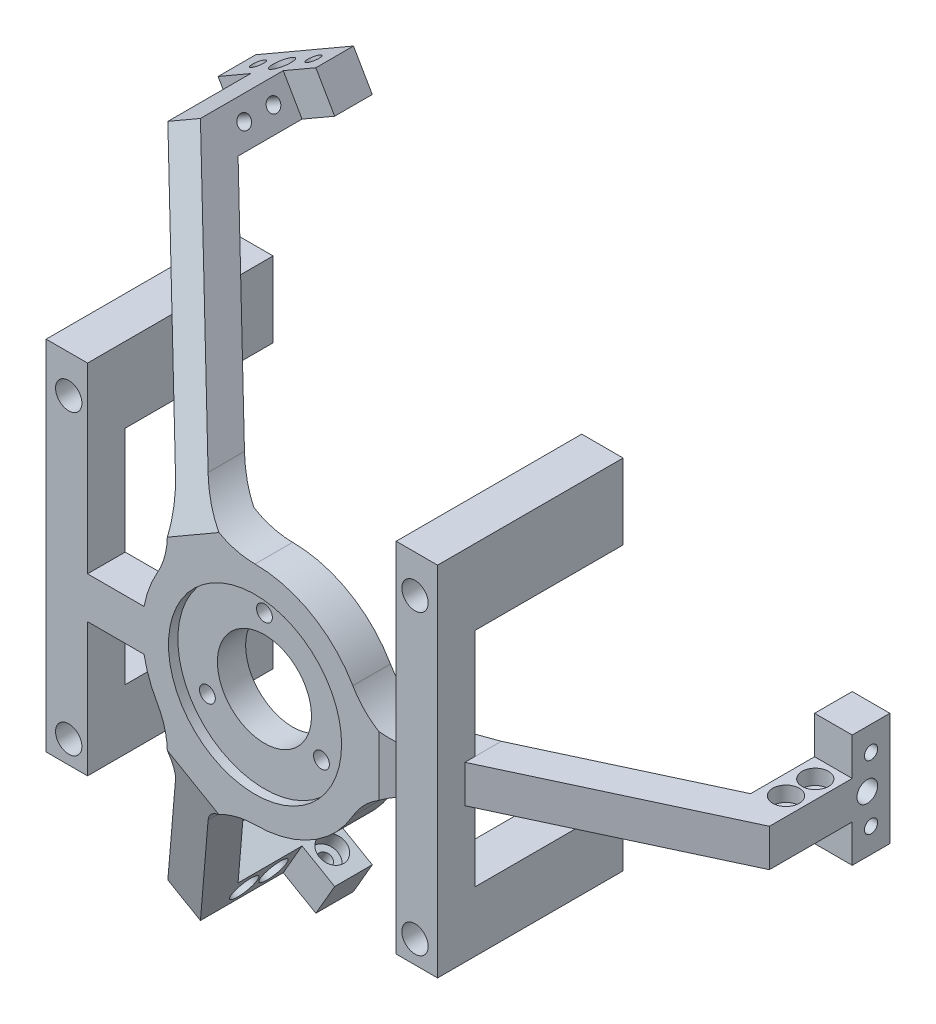
SolidWorks part; units mm, degrees
ref_plane "Plan de face" through (0, 0, 0) normal (0, 0, 1) x (1, 0, 0)
ref_plane "Plan de dessus" through (0, 0, 0) normal (0, 1, 0) x (1, 0, 0)
ref_plane "Plan de droite" through (0, 0, 0) normal (1, 0, 0) x (0, 0, -1)
sketch "Esquisse1" plane through (0, 0, 0) normal (0, 0, 1) x (1, 0, 0)
  line L0 (0, 0) -> (93.67, 0) construction
  line L1 (93.67, 15) -> (103.67, 15)
  line L2 (93.67, 15) -> (93.67, -15)
  line L3 (93.67, -15) -> (103.67, -15)
  line L4 (103.67, 15) -> (103.67, -15)
  line L5 (-33.8446, -88.6206) -> (-59.8254, -73.6206)
  line L6 (-33.8446, -88.6206) -> (-38.8446, -97.2809)
  line L7 (-38.8446, -97.2809) -> (-64.8254, -82.2809)
  line L8 (-59.8254, -73.6206) -> (-64.8254, -82.2809)
  line L9 (-59.8254, 73.6206) -> (-33.8446, 88.6206)
  line L10 (-59.8254, 73.6206) -> (-64.8254, 82.2809)
  line L11 (-64.8254, 82.2809) -> (-38.8446, 97.2809)
  line L12 (-33.8446, 88.6206) -> (-38.8446, 97.2809)
  point P17 (0, 0)
  dimension "D1" = 30
  dimension "D2" = 10
  dimension "D3" = 93.67
  dimension "D4" = 3
extrude "Boss.-Extru.1" add sketch "Esquisse1" along normal blind 10
sketch "Esquisse2" plane through (0, 0, 10) normal (0, 0, 1) x (1, 0, 0)
  line L0 (-57.0272, 86.7831) -> (-46.3532, 92.9458)
  line L1 (-38.8446, 97.2809) -> (-64.8254, 82.2809) construction
  line L2 (93.67, 15) -> (93.67, -15) construction
  line L3 (93.67, 5) -> (103.67, 5)
  line L4 (93.67, 5) -> (93.67, -5)
  line L5 (93.67, -5) -> (103.67, -5)
  line L6 (103.67, 5) -> (103.67, -5)
  line L7 (103.67, -15) -> (103.67, 15) construction
  line L8 (-42.5049, -83.6206) -> (-51.1651, -78.6206)
  line L9 (-42.5049, -83.6206) -> (-47.5049, -92.2809)
  line L10 (-47.5049, -92.2809) -> (-56.1651, -87.2809)
  line L11 (-51.1651, -78.6206) -> (-56.1651, -87.2809)
  line L12 (-51.1651, 78.6206) -> (-42.5049, 83.6206)
  line L13 (-51.1651, 78.6206) -> (-56.1651, 87.2809)
  line L14 (-56.1651, 87.2809) -> (-47.5049, 92.2809)
  line L15 (-42.5049, 83.6206) -> (-47.5049, 92.2809)
  point P12 (93.67, 0)
  point P13 (93.67, 0)
  point P24 (0, 0)
  line M6 (-59.8254, 73.6206) -> (-33.8446, 88.6206)
  dimension "D1" = 3
extrude "Boss.-Extru.2" add sketch "Esquisse2" along normal blind 45 contours L15 L0 L13 M6 | L6 L3 L4 L5 | L8 L11 L10 L9 region at (-49.335, 85.4507, 10) region at (98.67, 0, 10) region at (-49.335, -85.4507, 10)
sketch "Esquisse3" plane through (0, 0, 55) normal (0, 0, 1) x (1, 0, 0)
  line L0 (103.67, 5) -> (103.67, -5) construction
  line L1 (-47.5049, -92.2809) -> (-56.1651, -87.2809) construction
  line L2 (-47.5049, 92.2809) -> (-56.1651, 87.2809) construction
  line L3 (103.67, 5) -> (103.67, -5)
  line L4 (-47.5049, -92.2809) -> (-56.1651, -87.2809)
  line L5 (-47.5049, 92.2809) -> (-56.1651, 87.2809)
  line L6 (-56.1651, -87.2809) -> (-19.1203, -23.1174)
  line L7 (-47.5049, -92.2809) -> (-10.4601, -28.1174)
  line L8 (103.67, -5) -> (29.5804, -5)
  line L9 (103.67, 5) -> (29.5804, 5)
  line L10 (-56.1651, 87.2809) -> (-19.1203, 23.1174)
  line L11 (-47.5049, 92.2809) -> (-10.4601, 28.1174)
  line L12 (-51.1651, -78.6206) -> (-56.1651, -87.2809) construction
  line L13 (-42.5049, -83.6206) -> (-47.5049, -92.2809) construction
  line L14 (93.67, -5) -> (103.67, -5) construction
  line L15 (93.67, 5) -> (103.67, 5) construction
  line L16 (-51.1651, 78.6206) -> (-56.1651, 87.2809) construction
  line L17 (-42.5049, 83.6206) -> (-47.5049, 92.2809) construction
  arc A0 (-19.1203, -23.1174) -> (-19.1203, 23.1174) centre (0, 0) cw
  arc A1 (-10.4601, 28.1174) -> (29.5804, 5) centre (0, 0) cw
  arc A2 (29.5804, -5) -> (-10.4601, -28.1174) centre (0, 0) cw
  dimension "D1" = 30
extrude "Boss.-Extru.3" add sketch "Esquisse3" along normal blind 10
chamfer "Chanfrein1" distance 28 angle 65 3 edges at (93.67, 0, 55) (-46.835, -81.1206, 55) (-46.835, 81.1206, 55) first distance on face at (93.67, 0, 18.75) first distance on face at (-46.835, -81.1206, 18.75) first distance on face at (-46.835, 81.1206, 18.75)
chamfer "Chanfrein2" distance 33 angle 65 3 edges at (-51.835, -89.7809, 65) (-51.835, 89.7809, 65) (103.67, 0, 65) first distance on face at (-51.835, -89.7809, 21.25) first distance on face at (-51.835, 89.7809, 21.25) first distance on face at (103.67, 0, 21.25)
fillet "Congé1" radius 20 6 edges at (29.5804, -5, 60) (-10.4601, -28.1174, 60) (-19.1203, -23.1174, 60) (-19.1203, 23.1174, 60) (29.5804, 5, 60) (-10.4601, 28.1174, 60)
sketch "Esquisse4" plane through (0, 0, 65) normal (0, 0, 1) x (1, 0, 0)
  circle A0 centre (0, 0) radius 12.5
  dimension "D1" = 25
extrude "Enlèv. mat.-Extru.1" cut sketch "Esquisse4" against normal up to next
sketch "Esquisse5" plane through (0, 0, 65) normal (0, 0, 1) x (1, 0, 0)
  circle A0 centre (0, 0) radius 23
  dimension "D1" = 46
extrude "Enlèv. mat.-Extru.2" cut sketch "Esquisse5" against normal blind 2.5
sketch "Esquisse6" plane through (0, 0, 62.5) normal (0, 0, 1) x (1, 0, 0)
  line L0 (0, 17.5) -> (0, 0) construction
  circle A0 centre (0, 17.5) radius 2.1
  circle A1 centre (15.1554, -8.75) radius 2.1
  circle A2 centre (-15.1554, -8.75) radius 2.1
  point P10 (0, 0)
  dimension "D2" = 4.2
  dimension "D1" = 17.5
  dimension "D3" = 3
extrude "Enlèv. mat.-Extru.3" cut sketch "Esquisse6" against normal up to next
sketch "Esquisse7" plane through (0, 0, 55) normal (0, 0, -1) x (-1, 0, 0)
  line L0 (0, 0) -> (44.5, 0) construction
  line L1 (-37.5, -41) -> (-48.5, -41)
  line L2 (-37.5, -41) -> (-37.5, 54)
  line L3 (-37.5, 54) -> (-48.5, 54)
  line L4 (-48.5, -41) -> (-48.5, 54)
  line L5 (55.5, -41) -> (44.5, -41)
  line L6 (44.5, -41) -> (44.5, -5.5)
  line L7 (44.5, -5.5) -> (29.4915, -5.5)
  line L8 (55.5, -41) -> (55.5, 54)
  line L9 (55.5, 54) -> (44.5, 54)
  line L10 (44.5, 54) -> (44.5, 5.5)
  line L11 (44.5, 5.5) -> (29.4915, 5.5)
  line L12 (44.5, -5.5) -> (44.5, 5.5) construction
  arc A0 (25.9808, -15) -> (25.9808, 15) centre (0, 0) ccw construction
  arc A1 (29.4915, -5.5) -> (29.4915, 5.5) centre (0, 0) ccw
  point P7 (-43, 54)
  point P22 (44.5, 0)
  point P28 (50, 54)
  dimension "D1" = 11
  dimension "D2" = 41
  dimension "D3" = 95
  dimension "D4" = 43
  dimension "D5" = 93
extrude "Boss.-Extru.4" add sketch "Esquisse7" along normal blind 39.3 and the other way up to surface (10 mm away) other way up to face at (23, 0, 65)
sketch "Esquisse8" plane through (0, 0, 15.7) normal (0, 0, -1) x (-1, 0, 0)
  line L0 (-48.5, 6.5) -> (55.5, 6.5) construction
  line L1 (-48.5, 54) -> (-48.5, -41) construction
  line L2 (55.5, -41) -> (55.5, 54) construction
  line L3 (49.5, 44) -> (-42.5, 44) construction
  line L4 (3.5, 6.5) -> (3.5, 44) construction
  line L5 (-48.5, -41) -> (-37.5, -41) construction
  circle A0 centre (49.5, 44) radius 1.75
  circle A1 centre (-42.5, 44) radius 1.75
  circle A2 centre (-42.5, -35) radius 1.75
  circle A3 centre (49.5, -35) radius 1.75
  dimension "D4" = 3.5
  dimension "D1" = 92
  dimension "D2" = 79
  dimension "D3" = 6
extrude "Enlèv. mat.-Extru.4" cut sketch "Esquisse8" against normal up to next
sketch "Esquisse9" plane through (0, 0, 65) normal (0, 0, 1) x (1, 0, 0)
  circle A0 centre (42.5, -35) radius 3.5
  circle A1 centre (42.5, 44) radius 3.5
  circle A2 centre (-49.5, -35) radius 3.5
  circle A3 centre (-49.5, 44) radius 3.5
  dimension "D1" = 7
extrude "Enlèv. mat.-Extru.5" cut sketch "Esquisse9" against normal offset from surface (28.3 mm away) 21 up to face at (40.75, -35, 15.7)
sketch "Esquisse10" plane through (0, 0, 15.7) normal (0, 0, -1) x (-1, 0, 0)
  line L6 (55.5, -41) -> (55.5, 54) construction
  line L7 (55.5, -25) -> (29.4915, -25)
  line L8 (55.5, -25) -> (55.5, 34)
  line L9 (55.5, 34) -> (29.4915, 34)
  line L10 (29.4915, -25) -> (29.4915, 34)
  line L11 (49.5, 44) -> (49.5, 34) construction
  line L12 (49.5, -35) -> (49.5, -25) construction
  line L13 (-48.5, 54) -> (-48.5, -41) construction
  line L14 (-48.5, 34) -> (-37.5, 34)
  line L15 (-48.5, 34) -> (-48.5, -25)
  line L16 (-48.5, -25) -> (-37.5, -25)
  line L17 (-37.5, 34) -> (-37.5, -25)
  line L18 (-37.5, -41) -> (-37.5, 54) construction
  dimension "D1" = 10
extrude "Enlèv. mat.-Extru.6" cut sketch "Esquisse10" against normal up to surface (39.3 mm away) up to face at (-2.1, 17.5, 55)
sketch "Esquisse17" plane through (0, 0, 55) normal (0, 0, -1) x (-1, 0, 0)
  line L0 (-37.5, -5.8599) -> (-48.5, -5)
  line L1 (-48.5, -5) -> (-48.5, 5)
  line L2 (-48.5, 5) -> (-37.5, 5.8599)
  line L3 (-37.5, 5.8599) -> (-37.5, -5.8599)
extrude "Boss.-Extru.5" add sketch "Esquisse17" along normal up to surface (6.9369 mm away) contours L3 L0 L1 L2 up to face at (71.085, 0, 37.5316)
sketch "Esquisse11" plane through (4.3301, -2.5, 0) normal (0.866, -0.5, 0) x (0, 0, -1)
  line L0 (-27, -93.67) -> (-10, -93.67) construction
  line L1 (-10, -93.67) -> (-10, -103.67) construction
  circle A0 centre (-15, -98.86) radius 1.75
  circle A1 centre (-22.78, -98.86) radius 1.75
  dimension "D4" = 3.5
  dimension "D1" = 5.19
  dimension "D2" = 5
  dimension "D3" = 7.78
extrude "Enlèv. mat.-Extru.7" cut sketch "Esquisse11" against normal up to next
sketch "Esquisse12" plane through (4.3301, -2.5, 0) normal (0.866, -0.5, 0) x (0, 0, -1)
  circle A0 centre (-15, -98.86) radius 3.5
  circle A1 centre (-22.78, -98.86) radius 3.5
  dimension "D1" = 7
extrude "Enlèv. mat.-Extru.8" cut sketch "Esquisse12" against normal blind 4
sketch "Esquisse13" plane through (-46.835, -81.1206, 0) normal (0.5, 0.866, 0) x (0.866, -0.5, 0)
  line L0 (-15, -10) -> (-15, 0) construction
  line L1 (-15, -5) -> (-8.5, -5) construction
  line L2 (15, -5) -> (8.5, -5) construction
  line L3 (15, -10) -> (15, 0) construction
  circle A0 centre (-8.5, -5) radius 1.75
  circle A1 centre (8.5, -5) radius 1.75
  dimension "D2" = 3.5
  dimension "D1" = 6.5
extrude "Enlèv. mat.-Extru.9" cut sketch "Esquisse13" against normal up to next
sketch "Esquisse14" plane through (-46.835, -81.1206, 0) normal (0.5, 0.866, 0) x (0.866, -0.5, 0)
  circle A0 centre (-8.5, -5) radius 3.5
  circle A1 centre (8.5, -5) radius 3.5
  dimension "D1" = 7
extrude "Enlèv. mat.-Extru.10" cut sketch "Esquisse14" against normal blind 4
sketch "Esquisse15" plane through (-46.835, -81.1206, 0) normal (0.5, 0.866, 0) x (0.866, -0.5, 0)
  line L0 (15, 0) -> (-15, 0) construction
  line L1 (-15, -10) -> (-15, 0) construction
  circle A0 centre (0, -6) radius 2.75
  point P5 (0, 0)
  point P8 (-15, -5)
  dimension "D1" = 5.5
  dimension "D2" = 1
extrude "Enlèv. mat.-Extru.11" cut sketch "Esquisse15" against normal up to next
pattern_circular "Répétition circulaire1" count 3 over 360 about axis through (0, 0, -0.001) along (0, 0, 1) of "Enlèv. mat.-Extru.7", "Enlèv. mat.-Extru.11", "Enlèv. mat.-Extru.10", "Enlèv. mat.-Extru.9", "Enlèv. mat.-Extru.8" reverse direction yes
